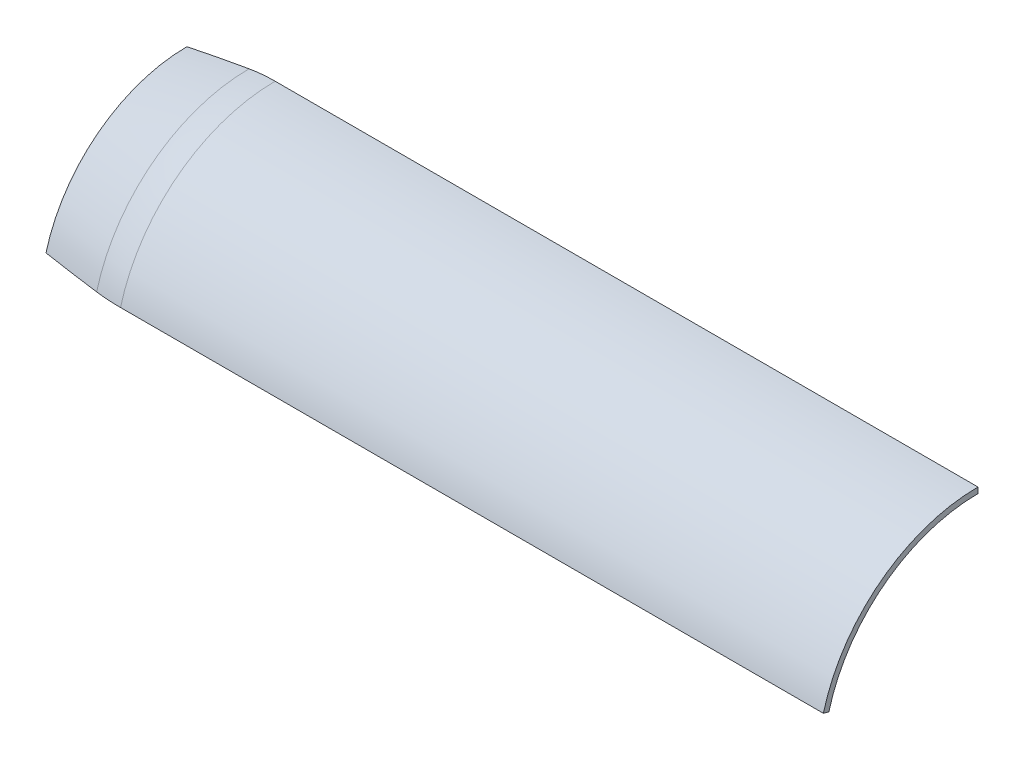
SolidWorks part; units mm, degrees
ref_plane "Front Plane" through (0, 0, 0) normal (0, 0, 1) x (1, 0, 0)
ref_plane "Top Plane" through (0, 0, 0) normal (0, 1, 0) x (1, 0, 0)
ref_plane "Right Plane" through (0, 0, 0) normal (1, 0, 0) x (0, 0, -1)
curve "Curve1"
  spline degree 3 poles (0, 0, 0) (-0.0123, 3.8916, 0) (-0.0274, 8.685, 0) (0.3616, 14.0857, 0) (0.5761, 16.0905, 0) (0.7825, 17.6048, 0) (0.9862, 18.8543, 0) (1.1887, 19.9315, 0) (1.3904, 20.8857, 0) (1.5917, 21.7465, 0) (1.7927, 22.5337, 0) (1.9935, 23.2611, 0) (2.1942, 23.9386, 0) (2.3947, 24.5739, 0) (2.5952, 25.1728, 0) (2.7956, 25.7401, 0) (2.9959, 26.2796, 0) (3.1962, 26.7943, 0) (3.3965, 27.2868, 0) (3.5967, 27.7594, 0) (3.7969, 28.2139, 0) (3.9971, 28.6519, 0) (4.1973, 29.0748, 0) (4.3974, 29.4838, 0) (4.5976, 29.8799, 0) (4.7977, 30.2641, 0) (4.9978, 30.6373, 0) (5.1979, 31.0001, 0) (5.398, 31.3533, 0) (5.5981, 31.6974, 0) (5.7982, 32.033, 0) (5.9983, 32.3606, 0) (6.1984, 32.6807, 0) (6.3985, 32.9935, 0) (6.5985, 33.2996, 0) (6.7986, 33.5993, 0) (6.9986, 33.8929, 0) (7.1987, 34.1806, 0) (7.3987, 34.4628, 0) (7.5988, 34.7397, 0) (7.7988, 35.0115, 0) (7.9989, 35.2785, 0) (8.1989, 35.5408, 0) (8.399, 35.7988, 0) (8.599, 36.0524, 0) (8.799, 36.3019, 0) (8.9991, 36.5476, 0) (9.1991, 36.7894, 0) (9.3991, 37.0275, 0) (9.5992, 37.2622, 0) (9.7992, 37.4934, 0) (9.9992, 37.7214, 0) (10.1992, 37.9461, 0) (10.3993, 38.1679, 0) (10.5993, 38.3866, 0) (10.7993, 38.6025, 0) (10.9993, 38.8156, 0) (11.1993, 39.026, 0) (11.3994, 39.2338, 0) (11.5994, 39.4391, 0) (11.7994, 39.6419, 0) (11.9994, 39.8422, 0) (12.1994, 40.0403, 0) (12.3995, 40.2361, 0) (12.5995, 40.4297, 0) (12.7995, 40.6212, 0) (12.9995, 40.8106, 0) (13.1995, 40.998, 0) (13.3995, 41.1834, 0) (13.5995, 41.3668, 0) (13.7995, 41.5484, 0) (13.9996, 41.7281, 0) (14.1996, 41.9061, 0) (14.3996, 42.0823, 0) (14.5996, 42.2568, 0) (14.7996, 42.4296, 0) (14.9996, 42.6008, 0) (15.1996, 42.7705, 0) (15.3996, 42.9385, 0) (15.5996, 43.1051, 0) (15.7996, 43.2701, 0) (15.9997, 43.4337, 0) (16.1997, 43.5959, 0) (16.3997, 43.7567, 0) (16.5997, 43.9161, 0) (16.7997, 44.0742, 0) (16.9997, 44.2309, 0) (17.1997, 44.3864, 0) (17.3997, 44.5406, 0) (17.5997, 44.6936, 0) (17.7997, 44.8453, 0) (17.9997, 44.9959, 0) (18.1997, 45.1453, 0) (18.3997, 45.2936, 0) (18.5997, 45.4407, 0) (18.7997, 45.5868, 0) (18.9997, 45.7317, 0) (19.1998, 45.8756, 0) (19.3998, 46.0185, 0) (19.5998, 46.1603, 0) (19.7998, 46.3011, 0) (19.9998, 46.4409, 0) (20.1998, 46.5797, 0) (20.3998, 46.7176, 0) (20.5998, 46.8546, 0) (20.7998, 46.9906, 0) (20.9998, 47.1257, 0) (21.1998, 47.2599, 0) (21.3998, 47.3932, 0) (21.5998, 47.5256, 0) (21.7998, 47.6572, 0) (21.9998, 47.788, 0) (22.1998, 47.9179, 0) (22.3998, 48.047, 0) (22.5998, 48.1753, 0) (22.7998, 48.3028, 0) (22.9998, 48.4295, 0) (23.1998, 48.5555, 0) (23.3998, 48.6807, 0) (23.5998, 48.8051, 0) (23.7998, 48.9288, 0) (23.9998, 49.0518, 0) (24.1998, 49.1741, 0) (24.3998, 49.2957, 0) (24.5998, 49.4165, 0) (24.7999, 49.5367, 0) (24.9999, 49.6562, 0) (25.1999, 49.7751, 0) (25.3999, 49.8933, 0) (25.5999, 50.0108, 0) (25.7999, 50.1277, 0) (25.9999, 50.2439, 0) (26.1999, 50.3596, 0) (26.3999, 50.4746, 0) (26.5999, 50.589, 0) (26.7999, 50.7028, 0) (26.9999, 50.8161, 0) (27.1999, 50.9287, 0) (27.3999, 51.0407, 0) (27.5999, 51.1522, 0) (27.7999, 51.2631, 0) (27.9999, 51.3735, 0) (28.1999, 51.4833, 0) (28.3999, 51.5926, 0) (28.5999, 51.7013, 0) (28.7999, 51.8095, 0) (28.9999, 51.9172, 0) (29.1999, 52.0243, 0) (29.3999, 52.131, 0) (29.5999, 52.2371, 0) (29.7999, 52.3428, 0) (29.9999, 52.4479, 0) (30.1999, 52.5526, 0) (30.3999, 52.6567, 0) (30.5999, 52.7604, 0) (30.7999, 52.8636, 0) (30.9999, 52.9664, 0) (31.1999, 53.0687, 0) (31.3999, 53.1705, 0) (31.5999, 53.2719, 0) (31.7999, 53.3728, 0) (31.9999, 53.4733, 0) (32.1999, 53.5733, 0) (32.3999, 53.6729, 0) (32.5999, 53.7721, 0) (32.7999, 53.8709, 0) (32.9999, 53.9692, 0) (33.1999, 54.0671, 0) (33.3999, 54.1646, 0) (33.5999, 54.2617, 0) (33.7999, 54.3584, 0) (33.9999, 54.4547, 0) (34.1999, 54.5506, 0) (34.3999, 54.6461, 0) (34.5999, 54.7412, 0) (34.7999, 54.836, 0) (34.9999, 54.9303, 0) (35.1999, 55.0243, 0) (35.3999, 55.1179, 0) (35.5999, 55.2111, 0) (35.7999, 55.304, 0) (35.9999, 55.3965, 0) (36.1999, 55.4887, 0) (36.3999, 55.5805, 0) (36.5999, 55.6719, 0) (36.7999, 55.763, 0) (36.9999, 55.8537, 0) (37.1999, 55.9441, 0) (37.3999, 56.0342, 0) (37.5999, 56.1239, 0) (37.7999, 56.2133, 0) (37.9999, 56.3024, 0) (38.1999, 56.3911, 0) (38.3999, 56.4795, 0) (38.5999, 56.5676, 0) (38.7999, 56.6554, 0) (38.9999, 56.7428, 0) (39.1999, 56.83, 0) (39.3999, 56.9168, 0) (39.5999, 57.0033, 0) (39.7999, 57.0896, 0) (39.9999, 57.1755, 0) (40.1999, 57.2611, 0) (40.3999, 57.3464, 0) (40.5999, 57.4314, 0) (40.7999, 57.5161, 0) (40.9999, 57.6006, 0) (41.1999, 57.6847, 0) (41.3999, 57.7686, 0) (41.6, 57.8522, 0) (41.8, 57.9355, 0) (42, 58.0185, 0) (42.2, 58.1012, 0) (42.4, 58.1837, 0) (42.6, 58.2659, 0) (42.8, 58.3479, 0) (43, 58.4295, 0) (43.2, 58.5109, 0) (43.4, 58.592, 0) (43.6, 58.6729, 0) (43.8, 58.7535, 0) (44, 58.8339, 0) (44.2, 58.914, 0) (44.4, 58.9938, 0) (44.6, 59.0734, 0) (44.8, 59.1528, 0) (45, 59.2319, 0) (45.2, 59.3107, 0) (45.4, 59.3893, 0) (45.6, 59.4677, 0) (45.8, 59.5458, 0) (46, 59.6237, 0) (46.2, 59.7014, 0) (46.4, 59.7788, 0) (46.6, 59.856, 0) (46.8, 59.9329, 0) (47, 60.0096, 0) (47.2, 60.0861, 0) (47.4, 60.1624, 0) (47.6, 60.2385, 0) (47.8, 60.3143, 0) (48, 60.3899, 0) (48.2, 60.4652, 0) (48.4, 60.5404, 0) (48.6, 60.6153, 0) (48.8, 60.6901, 0) (49, 60.7646, 0) (49.2, 60.8389, 0) (49.4, 60.913, 0) (49.6, 60.9869, 0) (49.8, 61.0605, 0) (50, 61.134, 0) (50.2, 61.2072, 0) (50.4, 61.2803, 0) (50.6, 61.3531, 0) (50.8, 61.4258, 0) (51, 61.4982, 0) (51.2, 61.5705, 0) (51.4, 61.6426, 0) (51.6, 61.7144, 0) (51.8, 61.7861, 0) (52, 61.8575, 0) (52.2, 61.9288, 0) (52.4, 61.9999, 0) (52.6, 62.0708, 0) (52.8, 62.1415, 0) (53, 62.212, 0) (53.2, 62.2824, 0) (53.4, 62.3525, 0) (53.6, 62.4225, 0) (53.8, 62.4923, 0) (54, 62.5619, 0) (54.2, 62.6313, 0) (54.4, 62.7006, 0) (54.6, 62.7696, 0) (54.8, 62.8385, 0) (55, 62.9072, 0) (55.2, 62.9758, 0) (55.4, 63.0441, 0) (55.6, 63.1123, 0) (55.8, 63.1803, 0) (56, 63.2482, 0) (56.2, 63.3159, 0) (56.4, 63.3834, 0) (56.6, 63.4507, 0) (56.8, 63.5179, 0) (57, 63.5849, 0) (57.2, 63.6518, 0) (57.4, 63.7185, 0) (57.6, 63.785, 0) (57.8, 63.8513, 0) (58, 63.9175, 0) (58.2, 63.9836, 0) (58.4, 64.0495, 0) (58.6, 64.1152, 0) (58.8, 64.1808, 0) (59, 64.2462, 0) (59.2, 64.3114, 0) (59.4, 64.3765, 0) (59.6, 64.4415, 0) (59.8, 64.5063, 0) (60, 64.5709, 0) (60.2, 64.6354, 0) (60.4, 64.6998, 0) (60.6, 64.764, 0) (60.8, 64.828, 0) (61, 64.8919, 0) (61.2, 64.9557, 0) (61.4, 65.0193, 0) (61.6, 65.0827, 0) (61.8, 65.1461, 0) (62, 65.2092, 0) (62.2, 65.2723, 0) (62.4, 65.3352, 0) (62.6, 65.3979, 0) (62.8, 65.4605, 0) (63, 65.523, 0) (63.2, 65.5853, 0) (63.4, 65.6475, 0) (63.6, 65.7096, 0) (63.8, 65.7715, 0) (64, 65.8333, 0) (64.2, 65.895, 0) (64.4, 65.9565, 0) (64.6, 66.0179, 0) (64.8, 66.0791, 0) (65, 66.1402, 0) (65.2, 66.2012, 0) (65.4, 66.2621, 0) (65.6, 66.3228, 0) (65.8, 66.3834, 0) (66, 66.4439, 0) (66.2, 66.5042, 0) (66.4, 66.5644, 0) (66.6, 66.6245, 0) (66.8, 66.6845, 0) (67, 66.7443, 0) (67.2, 66.804, 0) (67.4, 66.8636, 0) (67.6, 66.923, 0) (67.8, 66.9824, 0) (68, 67.0416, 0) (68.2, 67.1007, 0) (68.4, 67.1597, 0) (68.6, 67.2185, 0) (68.8, 67.2772, 0) (69, 67.3359, 0) (69.2, 67.3943, 0) (69.4, 67.4527, 0) (69.6, 67.511, 0) (69.8, 67.5691, 0) (70, 67.6271, 0) (70.2, 67.6851, 0) (70.4, 67.7428, 0) (70.6, 67.8005, 0) (70.8, 67.8581, 0) (71, 67.9155, 0) (71.2, 67.9729, 0) (71.4, 68.0301, 0) (71.6, 68.0872, 0) (71.8, 68.1442, 0) (72, 68.2011, 0) (72.2, 68.2579, 0) (72.4, 68.3145, 0) (72.6, 68.3711, 0) (72.8, 68.4276, 0) (73, 68.4839, 0) (73.2, 68.5401, 0) (73.4, 68.5963, 0) (73.6, 68.6523, 0) (73.8, 68.7082, 0) (74, 68.764, 0) (74.2, 68.8197, 0) (74.4, 68.8753, 0) (74.6, 68.9308, 0) (74.8, 68.9862, 0) (75, 69.0415, 0) (75.2, 69.0966, 0) (75.4, 69.1517, 0) (75.6, 69.2067, 0) (75.8, 69.2616, 0) (76, 69.3164, 0) (76.2, 69.371, 0) (76.4, 69.4256, 0) (76.6, 69.4801, 0) (76.8, 69.5344, 0) (77, 69.5887, 0) (77.2, 69.6429, 0) (77.4, 69.697, 0) (77.6, 69.751, 0) (77.8, 69.8048, 0) (78, 69.8586, 0) (78.2, 69.9123, 0) (78.4, 69.9659, 0) (78.6, 70.0194, 0) (78.8, 70.0728, 0) (79, 70.1261, 0) (79.2, 70.1793, 0) (79.4, 70.2324, 0) (79.6, 70.2855, 0) (79.8, 70.3384, 0) (80, 70.3912, 0) (80.2, 70.444, 0) (80.4, 70.4966, 0) (80.6, 70.5492, 0) (80.8, 70.6017, 0) (81, 70.6541, 0) (81.2, 70.7064, 0) (81.4, 70.7586, 0) (81.6, 70.8107, 0) (81.8, 70.8627, 0) (82, 70.9146, 0) (82.2, 70.9665, 0) (82.4, 71.0182, 0) (82.6, 71.0699, 0) (82.8, 71.1215, 0) (83, 71.173, 0) (83.2, 71.2244, 0) (83.4, 71.2757, 0) (83.6, 71.3269, 0) (83.8, 71.3781, 0) (84, 71.4291, 0) (84.2, 71.4801, 0) (84.4, 71.531, 0) (84.6, 71.5818, 0) (84.8, 71.6325, 0) (85, 71.6832, 0) (85.2, 71.7337, 0) (85.4, 71.7842, 0) (85.6, 71.8346, 0) (85.8, 71.8849, 0) (86, 71.9351, 0) (86.2, 71.9853, 0) (86.4, 72.0354, 0) (86.6, 72.0853, 0) (86.8, 72.1352, 0) (87, 72.1851, 0) (87.2, 72.2348, 0) (87.4, 72.2845, 0) (87.6, 72.3341, 0) (87.8, 72.3836, 0) (88, 72.433, 0) (88.2, 72.4823, 0) (88.4, 72.5316, 0) (88.6, 72.5808, 0) (88.8, 72.6299, 0) (89, 72.6789, 0) (89.2, 72.7279, 0) (89.4, 72.7768, 0) (89.6, 72.8256, 0) (89.8, 72.8743, 0) (90, 72.923, 0) (90.2, 72.9716, 0) (90.4, 73.0201, 0) (90.6, 73.0685, 0) (90.8, 73.1168, 0) (91, 73.1651, 0) (91.2, 73.2133, 0) (91.4, 73.2614, 0) (91.6, 73.3095, 0) (91.8, 73.3575, 0) (92, 73.4054, 0) (92.2, 73.4532, 0) (92.4, 73.501, 0) (92.6, 73.5487, 0) (92.8, 73.5963, 0) (93, 73.6439, 0) (93.2, 73.6913, 0) (93.4, 73.7387, 0) (93.6, 73.7861, 0) (93.8, 73.8333, 0) (94, 73.8805, 0) (94.2, 73.9276, 0) (94.4, 73.9747, 0) (94.6, 74.0217, 0) (94.8, 74.0686, 0) (95, 74.1154, 0) (95.2, 74.1622, 0) (95.4, 74.2089, 0) (95.6, 74.2556, 0) (95.8, 74.3021, 0) (96, 74.3486, 0) (96.2, 74.3951, 0) (96.4, 74.4414, 0) (96.6, 74.4877, 0) (96.8, 74.534, 0) (97, 74.5801, 0) (97.2, 74.6262, 0) (97.4, 74.6723, 0) (97.6, 74.7182, 0) (97.8, 74.7641, 0) (98, 74.81, 0) (98.2, 74.8557, 0) (98.4, 74.9014, 0) (98.6, 74.9471, 0) (98.8, 74.9926, 0) (99, 75.0382, 0) (99.2, 75.0836, 0) (99.4, 75.129, 0) (99.6, 75.1743, 0) (99.8, 75.2196, 0) (100, 75.2647, 0) (100.2, 75.3099, 0) (100.4, 75.3549, 0) (100.6, 75.3999, 0) (100.8, 75.4449, 0) (101, 75.4898, 0) (101.2, 75.5346, 0) (101.4, 75.5793, 0) (101.6, 75.624, 0) (101.8, 75.6686, 0) (102, 75.7132, 0) (102.2, 75.7577, 0) (102.4, 75.8022, 0) (102.6, 75.8465, 0) (102.8, 75.8909, 0) (103, 75.9351, 0) (103.2, 75.9793, 0) (103.4, 76.0235, 0) (103.6, 76.0676, 0) (103.8, 76.1116, 0) (104, 76.1556, 0) (104.2, 76.1995, 0) (104.4, 76.2433, 0) (104.6, 76.2871, 0) (104.8, 76.3308, 0) (105, 76.3745, 0) (105.2, 76.4181, 0) (105.4, 76.4617, 0) (105.6, 76.5052, 0) (105.8, 76.5486, 0) (106, 76.592, 0) (106.2, 76.6353, 0) (106.4, 76.6786, 0) (106.6, 76.7218, 0) (106.8, 76.7649, 0) (107, 76.808, 0) (107.2, 76.8511, 0) (107.4, 76.8941, 0) (107.6, 76.937, 0) (107.8, 76.9799, 0) (108, 77.0227, 0) (108.2, 77.0655, 0) (108.4, 77.1082, 0) (108.6, 77.1508, 0) (108.8, 77.1934, 0) (109, 77.236, 0) (109.2, 77.2784, 0) (109.4, 77.3209, 0) (109.6, 77.3633, 0) (109.8, 77.4056, 0) (110, 77.4479, 0) (110.2, 77.4901, 0) (110.4, 77.5322, 0) (110.6, 77.5743, 0) (110.8, 77.6164, 0) (111, 77.6584, 0) (111.2, 77.7004, 0) (111.4, 77.7423, 0) (111.6, 77.7841, 0) (111.8, 77.8259, 0) (112, 77.8676, 0) (112.2, 77.9093, 0) (112.4, 77.951, 0) (112.6, 77.9925, 0) (112.8, 78.0341, 0) (113, 78.0756, 0) (113.2, 78.117, 0) (113.4, 78.1584, 0) (113.6, 78.1997, 0) (113.8, 78.241, 0) (114, 78.2822, 0) (114.2, 78.3234, 0) (114.4, 78.3645, 0) (114.6, 78.4056, 0) (114.8, 78.4466, 0) (115, 78.4876, 0) (115.2, 78.5285, 0) (115.4, 78.5694, 0) (115.6, 78.6102, 0) (115.8, 78.651, 0) (116, 78.6917, 0) (116.2, 78.7324, 0) (116.4, 78.773, 0) (116.6, 78.8136, 0) (116.8, 78.8541, 0) (117, 78.8946, 0) (117.2, 78.935, 0) (117.4, 78.9754, 0) (117.6, 79.0158, 0) (117.8, 79.0561, 0) (118, 79.0963, 0) (118.2, 79.1365, 0) (118.4, 79.1766, 0) (118.6, 79.2167, 0) (118.8, 79.2568, 0) (119, 79.2968, 0) (119.2, 79.3368, 0) (119.4, 79.3767, 0) (119.6, 79.4165, 0) (119.8, 79.4564, 0) (120, 79.4961, 0) (120.2, 79.5358, 0) (120.4, 79.5755, 0) (120.6, 79.6152, 0) (120.8, 79.6547, 0) (121, 79.6943, 0) (121.2, 79.7338, 0) (121.4, 79.7732, 0) (121.6, 79.8126, 0) (121.8, 79.852, 0) (122, 79.8913, 0) (122.2, 79.9306, 0) (122.4, 79.9698, 0) (122.6, 80.009, 0) (122.8, 80.0481, 0) (123, 80.0872, 0) (123.2, 80.1262, 0) (123.4, 80.1652, 0) (123.6, 80.2042, 0) (123.8, 80.2431, 0) (124, 80.282, 0) (124.2, 80.3208, 0) (124.4, 80.3596, 0) (124.6, 80.3983, 0) (124.8, 80.437, 0) (125, 80.4757, 0) (125.2, 80.5143, 0) (125.4, 80.5528, 0) (125.6, 80.5914, 0) (125.8, 80.6298, 0) (126, 80.6683, 0) (126.2, 80.7067, 0) (126.4, 80.745, 0) (126.6, 80.7833, 0) (126.8, 80.8216, 0) (127, 80.8598, 0) (127.2, 80.898, 0) (127.4, 80.9361, 0) (127.6, 80.9742, 0) (127.8, 81.0123, 0) (128, 81.0503, 0) (128.2, 81.0883, 0) (128.4, 81.1262, 0) (128.6, 81.1641, 0) (128.8, 81.2019, 0) (129, 81.2397, 0) (129.2, 81.2775, 0) (129.4, 81.3152, 0) (129.6, 81.3529, 0) (129.8, 81.3906, 0) (130, 81.4282, 0) (130.2, 81.4657, 0) (130.4, 81.5032, 0) (130.6, 81.5407, 0) (130.8, 81.5782, 0) (131, 81.6156, 0) (131.2, 81.6529, 0) (131.4, 81.6902, 0) (131.6, 81.7275, 0) (131.8, 81.7648, 0) (132, 81.802, 0) (132.2, 81.8391, 0) (132.4, 81.8763, 0) (132.6, 81.9133, 0) (132.8, 81.9504, 0) (133, 81.9874, 0) (133.2, 82.0244, 0) (133.4, 82.0613, 0) (133.6, 82.0982, 0) (133.8, 82.135, 0) (134, 82.1718, 0) (134.2, 82.2086, 0) (134.4, 82.2454, 0) (134.6, 82.282, 0) (134.8, 82.3187, 0) (135, 82.3553, 0) (135.2, 82.3919, 0) (135.4, 82.4285, 0) (135.6, 82.465, 0) (135.8, 82.5014, 0) (136, 82.5379, 0) (136.2, 82.5743, 0) (136.4, 82.6106, 0) (136.6, 82.6469, 0) (136.8, 82.6832, 0) (137, 82.7195, 0) (137.2, 82.7557, 0) (137.4, 82.7919, 0) (137.6, 82.828, 0) (137.8, 82.8641, 0) (138, 82.9001, 0) (138.2, 82.9362, 0) (138.4, 82.9722, 0) (138.6, 83.0081, 0) (138.8, 83.044, 0) (139, 83.0799, 0) (139.2, 83.1158, 0) (139.4, 83.1516, 0) (139.6, 83.1873, 0) (139.8, 83.2231, 0) (140, 83.2588, 0) (140.2, 83.2944, 0) (140.4, 83.3301, 0) (140.6, 83.3657, 0) (140.8, 83.4012, 0) (141, 83.4367, 0) (141.2, 83.4722, 0) (141.4, 83.5077, 0) (141.6, 83.5431, 0) (141.8, 83.5785, 0) (142, 83.6138, 0) (142.2, 83.6491, 0) (142.4, 83.6844, 0) (142.6, 83.7197, 0) (142.8, 83.7549, 0) (143, 83.79, 0) (143.2, 83.8252, 0) (143.4, 83.8603, 0) (143.6, 83.8954, 0) (143.8, 83.9304, 0) (144, 83.9654, 0) (144.2, 84.0004, 0) (144.4, 84.0353, 0) (144.6, 84.0702, 0) (144.8, 84.1051, 0) (145, 84.1399, 0) (145.2, 84.1747, 0) (145.4, 84.2095, 0) (145.6, 84.2442, 0) (145.8, 84.2789, 0) (146, 84.3136, 0) (146.2, 84.3482, 0) (146.4, 84.3828, 0) (146.6, 84.4174, 0) (146.8, 84.4519, 0) (147, 84.4864, 0) (147.2, 84.5209, 0) (147.4, 84.5553, 0) (147.6, 84.5897, 0) (147.8, 84.6241, 0) (148, 84.6584, 0) (148.2, 84.6927, 0) (148.4, 84.727, 0) (148.6, 84.7612, 0) (148.8, 84.7954, 0) (149, 84.8296, 0) (149.2, 84.8638, 0) (149.4, 84.8979, 0) (149.6, 84.9319, 0) (149.8, 84.966, 0) (149.9333, 84.9887, 0) (150, 85, 0) knots 0 0 0 0 0.061462 0.075706 0.085548 0.093322 0.099856 0.105554 0.110643 0.115268 0.119525 0.123482 0.127192 0.130691 0.13401 0.137173 0.140199 0.143104 0.145901 0.148602 0.151215 0.15375 0.156213 0.158609 0.160946 0.163227 0.165456 0.167638 0.169775 0.171871 0.173928 0.17595 0.177937 0.179893 0.181819 0.183716 0.185587 0.187433 0.189255 0.191054 0.192831 0.194589 0.196326 0.198045 0.199747 0.201431 0.2031 0.204753 0.206391 0.208015 0.209626 0.211223 0.212808 0.214381 0.215942 0.217493 0.219032 0.220561 0.22208 0.22359 0.225091 0.226582 0.228065 0.229539 0.231006 0.232464 0.233915 0.235359 0.236795 0.238225 0.239648 0.241065 0.242475 0.243879 0.245277 0.24667 0.248057 0.249438 0.250814 0.252185 0.253551 0.254913 0.256269 0.257621 0.258968 0.260311 0.26165 0.262984 0.264315 0.265641 0.266964 0.268282 0.269598 0.270909 0.272217 0.273522 0.274823 0.276121 0.277416 0.278707 0.279996 0.281281 0.282564 0.283843 0.28512 0.286394 0.287666 0.288935 0.290201 0.291465 0.292726 0.293985 0.295241 0.296495 0.297747 0.298996 0.300243 0.301489 0.302732 0.303972 0.305211 0.306448 0.307683 0.308916 0.310147 0.311376 0.312604 0.313829 0.315053 0.316275 0.317495 0.318714 0.319931 0.321147 0.32236 0.323573 0.324783 0.325993 0.3272 0.328406 0.329611 0.330815 0.332017 0.333217 0.334416 0.335614 0.336811 0.338006 0.3392 0.340393 0.341584 0.342775 0.343964 0.345152 0.346339 0.347524 0.348709 0.349892 0.351074 0.352256 0.353436 0.354615 0.355793 0.35697 0.358146 0.359321 0.360495 0.361668 0.36284 0.364011 0.365182 0.366351 0.36752 0.368687 0.369854 0.37102 0.372185 0.373349 0.374512 0.375674 0.376836 0.377997 0.379157 0.380316 0.381475 0.382632 0.383789 0.384946 0.386101 0.387256 0.38841 0.389563 0.390716 0.391868 0.393019 0.39417 0.39532 0.396469 0.397618 0.398766 0.399913 0.40106 0.402206 0.403351 0.404496 0.40564 0.406784 0.407927 0.409069 0.410211 0.411353 0.412493 0.413633 0.414773 0.415912 0.417051 0.418189 0.419326 0.420463 0.4216 0.422736 0.423871 0.425006 0.426141 0.427275 0.428408 0.429541 0.430674 0.431806 0.432937 0.434068 0.435199 0.436329 0.437459 0.438588 0.439717 0.440846 0.441974 0.443101 0.444229 0.445355 0.446482 0.447608 0.448733 0.449858 0.450983 0.452107 0.453231 0.454355 0.455478 0.456601 0.457723 0.458845 0.459967 0.461088 0.462209 0.46333 0.46445 0.46557 0.46669 0.467809 0.468928 0.470046 0.471164 0.472282 0.4734 0.474517 0.475634 0.47675 0.477866 0.478982 0.480098 0.481213 0.482328 0.483443 0.484557 0.485671 0.486785 0.487898 0.489011 0.490124 0.491237 0.492349 0.493461 0.494573 0.495684 0.496796 0.497906 0.499017 0.500127 0.501237 0.502347 0.503457 0.504566 0.505675 0.506784 0.507892 0.509001 0.510109 0.511216 0.512324 0.513431 0.514538 0.515645 0.516752 0.517858 0.518964 0.52007 0.521175 0.522281 0.523386 0.524491 0.525595 0.5267 0.527804 0.528908 0.530012 0.531116 0.532219 0.533322 0.534425 0.535528 0.53663 0.537733 0.538835 0.539937 0.541038 0.54214 0.543241 0.544342 0.545443 0.546544 0.547644 0.548745 0.549845 0.550945 0.552044 0.553144 0.554243 0.555342 0.556441 0.55754 0.558639 0.559737 0.560836 0.561934 0.563032 0.564129 0.565227 0.566324 0.567421 0.568518 0.569615 0.570712 0.571809 0.572905 0.574001 0.575097 0.576193 0.577289 0.578384 0.57948 0.580575 0.58167 0.582765 0.58386 0.584954 0.586049 0.587143 0.588237 0.589331 0.590425 0.591519 0.592612 0.593706 0.594799 0.595892 0.596985 0.598078 0.59917 0.600263 0.601355 0.602448 0.60354 0.604632 0.605724 0.606815 0.607907 0.608998 0.61009 0.611181 0.612272 0.613363 0.614453 0.615544 0.616635 0.617725 0.618815 0.619905 0.620995 0.622085 0.623175 0.624265 0.625354 0.626443 0.627533 0.628622 0.629711 0.6308 0.631888 0.632977 0.634066 0.635154 0.636242 0.637331 0.638419 0.639507 0.640594 0.641682 0.64277 0.643857 0.644945 0.646032 0.647119 0.648206 0.649293 0.65038 0.651467 0.652553 0.65364 0.654726 0.655813 0.656899 0.657985 0.659071 0.660157 0.661243 0.662328 0.663414 0.664499 0.665585 0.66667 0.667755 0.66884 0.669925 0.67101 0.672095 0.67318 0.674264 0.675349 0.676433 0.677518 0.678602 0.679686 0.68077 0.681854 0.682938 0.684022 0.685105 0.686189 0.687272 0.688356 0.689439 0.690522 0.691605 0.692688 0.693771 0.694854 0.695937 0.69702 0.698102 0.699185 0.700267 0.70135 0.702432 0.703514 0.704596 0.705678 0.70676 0.707842 0.708924 0.710006 0.711087 0.712169 0.71325 0.714332 0.715413 0.716494 0.717575 0.718656 0.719737 0.720818 0.721899 0.72298 0.724061 0.725141 0.726222 0.727302 0.728382 0.729463 0.730543 0.731623 0.732703 0.733783 0.734863 0.735943 0.737023 0.738103 0.739182 0.740262 0.741341 0.742421 0.7435 0.744579 0.745659 0.746738 0.747817 0.748896 0.749975 0.751054 0.752133 0.753211 0.75429 0.755369 0.756447 0.757526 0.758604 0.759682 0.760761 0.761839 0.762917 0.763995 0.765073 0.766151 0.767229 0.768307 0.769385 0.770462 0.77154 0.772618 0.773695 0.774773 0.77585 0.776927 0.778005 0.779082 0.780159 0.781236 0.782313 0.78339 0.784467 0.785544 0.786621 0.787698 0.788774 0.789851 0.790928 0.792004 0.793081 0.794157 0.795233 0.79631 0.797386 0.798462 0.799538 0.800614 0.80169 0.802766 0.803842 0.804918 0.805994 0.80707 0.808145 0.809221 0.810296 0.811372 0.812447 0.813523 0.814598 0.815674 0.816749 0.817824 0.818899 0.819974 0.821049 0.822124 0.823199 0.824274 0.825349 0.826424 0.827499 0.828573 0.829648 0.830723 0.831797 0.832872 0.833946 0.835021 0.836095 0.837169 0.838244 0.839318 0.840392 0.841466 0.84254 0.843614 0.844688 0.845762 0.846836 0.84791 0.848984 0.850058 0.851131 0.852205 0.853279 0.854352 0.855426 0.856499 0.857573 0.858646 0.859719 0.860793 0.861866 0.862939 0.864012 0.865085 0.866159 0.867232 0.868305 0.869378 0.87045 0.871523 0.872596 0.873669 0.874742 0.875814 0.876887 0.87796 0.879032 0.880105 0.881177 0.88225 0.883322 0.884395 0.885467 0.886539 0.887611 0.888684 0.889756 0.890828 0.8919 0.892972 0.894044 0.895116 0.896188 0.89726 0.898332 0.899404 0.900475 0.901547 0.902619 0.90369 0.904762 0.905834 0.906905 0.907977 0.909048 0.91012 0.911191 0.912262 0.913334 0.914405 0.915476 0.916548 0.917619 0.91869 0.919761 0.920832 0.921903 0.922974 0.924045 0.925116 0.926187 0.927258 0.928329 0.929399 0.93047 0.931541 0.932612 0.933682 0.934753 0.935823 0.936894 0.937965 0.939035 0.940105 0.941176 0.942246 0.943317 0.944387 0.945457 0.946527 0.947598 0.948668 0.949738 0.950808 0.951878 0.952948 0.954018 0.955088 0.956158 0.957228 0.958298 0.959368 0.960438 0.961508 0.962577 0.963647 0.964717 0.965786 0.966856 0.967926 0.968995 0.970065 0.971134 0.972204 0.973273 0.974343 0.975412 0.976481 0.977551 0.97862 0.979689 0.980759 0.981828 0.982897 0.983966 0.985035 0.986104 0.987173 0.988242 0.989311 0.99038 0.991449 0.992518 0.993587 0.994656 0.995725 0.996794 0.997863 0.998931 1 1 1 1
sketch "Sketch1" plane through (0, 0, 0) normal (0, 0, 1) x (1, 0, 0)
  line L0 (0, 0) -> (3, 0)
  line L1 (3, 0.0095) -> (3, 0)
  line L3 (150, 85) -> (530, 85)
  line L4 (150, 81.9569) -> (530, 81.9569)
  line L5 (530, 81.9569) -> (530, 85)
  line L6 (0, 0) -> (686.3935, 0) construction
  spline S0 degree 3 poles (-4988.3045, -127.8298) (181.331, -218.097) (-7.7458, -98.4721) (0.3616, 14.0857) (0.5761, 16.0905) (0.7825, 17.6048) (0.9862, 18.8543) (1.1887, 19.9315) (1.3904, 20.8857) (1.5917, 21.7465) (1.7927, 22.5337) (1.9935, 23.2611) (2.2538, 24.14) (2.5806, 25.1462) (2.9836, 26.2595) (3.3859, 27.2713) (3.7877, 28.2016) (4.1891, 29.0648) (4.5903, 29.8717) (5.0533, 30.7478) (5.5832, 31.6835) (6.1854, 32.6697) (6.7872, 33.5906) (7.4515, 34.5461) (8.1828, 35.531) (8.9851, 36.54) (9.8503, 37.5625) (10.7826, 38.5957) (11.785, 39.6369) (12.851, 40.6804) (13.984, 41.7246) (15.1862, 42.7682) (16.388, 43.7553) (17.6544, 44.7435) (18.9876, 45.7315) (20.3892, 46.7179) (21.7905, 47.6579) (23.2571, 48.5984) (24.7904, 49.5382) (26.3916, 50.4762) (28.0583, 51.4122) (29.7917, 52.3451) (31.5927, 53.2742) (33.4594, 54.1996) (35.3929, 55.1207) (37.4597, 56.0672) (39.5933, 57.0066) (41.8602, 57.9666) (44.1937, 58.9175) (46.6606, 59.8853) (49.2604, 60.8677) (51.994, 61.8617) (54.861, 62.8656) (57.7946, 63.8556) (60.8615, 64.8536) (64.0615, 65.8584) (67.4615, 66.8882) (70.9951, 67.9202) (74.6621, 68.9539) (78.4621, 69.9886) (82.4622, 71.0404) (86.6623, 72.1071) (91.0624, 73.1864) (95.6625, 74.2764) (100.4626, 75.3753) (105.4628, 76.4816) (110.6629, 77.5938) (116.063, 78.7107) (121.6632, 79.8312) (127.5299, 80.9671) (133.6633, 82.1162) (140.0634, 83.2764) (145.1985, 84.1774) (148.3332, 84.7158) (149.3333, 84.8865) (149.6, 84.9319) (210.4736, 95.2955) (272.2046, 100.2158) (-505.3505, 5038.0754) knots -1.697374 -1.697374 -1.697374 -1.697374 0.061462 0.075706 0.085548 0.093322 0.099856 0.105554 0.110643 0.115268 0.119525 0.123482 0.127192 0.13401 0.140199 0.145901 0.151215 0.156213 0.160946 0.165456 0.171871 0.177937 0.183716 0.189255 0.196326 0.2031 0.209626 0.217493 0.225091 0.232464 0.241065 0.249438 0.257621 0.265641 0.274823 0.283843 0.292726 0.301489 0.311376 0.321147 0.330815 0.341584 0.352256 0.36284 0.374512 0.386101 0.398766 0.411353 0.425006 0.438588 0.453231 0.468928 0.484557 0.501237 0.517858 0.535528 0.554243 0.574001 0.593706 0.614453 0.636242 0.659071 0.682938 0.707842 0.733783 0.760761 0.788774 0.817824 0.84791 0.879032 0.912262 0.946527 0.981828 0.994656 0.996794 0.997863 0.998931 1.972677 1.972677 1.972677 1.972677 only from (0, 0) to (150, 85) construction
  spline S1 degree 3 poles (0, 0) (-0.0123, 3.8916) (-0.0274, 8.685) (0.3616, 14.0857) (0.5761, 16.0905) (0.7825, 17.6048) (0.9862, 18.8543) (1.1887, 19.9315) (1.3904, 20.8857) (1.5917, 21.7465) (1.7927, 22.5337) (1.9935, 23.2611) (2.2538, 24.14) (2.5806, 25.1462) (2.9836, 26.2595) (3.3859, 27.2713) (3.7877, 28.2016) (4.1891, 29.0648) (4.5903, 29.8717) (5.0533, 30.7478) (5.5832, 31.6835) (6.1854, 32.6697) (6.7872, 33.5906) (7.4515, 34.5461) (8.1828, 35.531) (8.9851, 36.54) (9.8503, 37.5625) (10.7826, 38.5957) (11.785, 39.6369) (12.851, 40.6804) (13.984, 41.7246) (15.1862, 42.7682) (16.388, 43.7553) (17.6544, 44.7435) (18.9876, 45.7315) (20.3892, 46.7179) (21.7905, 47.6579) (23.2571, 48.5984) (24.7904, 49.5382) (26.3916, 50.4762) (28.0583, 51.4122) (29.7917, 52.3451) (31.5927, 53.2742) (33.4594, 54.1996) (35.3929, 55.1207) (37.4597, 56.0672) (39.5933, 57.0066) (41.8602, 57.9666) (44.1937, 58.9175) (46.6606, 59.8853) (49.2604, 60.8677) (51.994, 61.8617) (54.861, 62.8656) (57.7946, 63.8556) (60.8615, 64.8536) (64.0615, 65.8584) (67.4615, 66.8882) (70.9951, 67.9202) (74.6621, 68.9539) (78.4621, 69.9886) (82.4622, 71.0404) (86.6623, 72.1071) (91.0624, 73.1864) (95.6625, 74.2764) (100.4626, 75.3753) (105.4628, 76.4816) (110.6629, 77.5938) (116.063, 78.7107) (121.6632, 79.8312) (127.5299, 80.9671) (133.6633, 82.1162) (140.0634, 83.2764) (145.1985, 84.1774) (148.3332, 84.7158) (149.4, 84.8979) (149.7333, 84.9547) (149.9333, 84.9887) (150, 85) knots 0 0 0 0 0.061462 0.075706 0.085548 0.093322 0.099856 0.105554 0.110643 0.115268 0.119525 0.123482 0.127192 0.13401 0.140199 0.145901 0.151215 0.156213 0.160946 0.165456 0.171871 0.177937 0.183716 0.189255 0.196326 0.2031 0.209626 0.217493 0.225091 0.232464 0.241065 0.249438 0.257621 0.265641 0.274823 0.283843 0.292726 0.301489 0.311376 0.321147 0.330815 0.341584 0.352256 0.36284 0.374512 0.386101 0.398766 0.411353 0.425006 0.438588 0.453231 0.468928 0.484557 0.501237 0.517858 0.535528 0.554243 0.574001 0.593706 0.614453 0.636242 0.659071 0.682938 0.707842 0.733783 0.760761 0.788774 0.817824 0.84791 0.879032 0.912262 0.946527 0.981828 0.994656 0.996794 0.998931 1 1 1 1
  spline S2 degree 1 poles (3, 0.0095) (150.5029, 82.0425) knots 0 0 1 1 construction
  spline S3 degree 3 poles (3, 0.0095) (2.9938, 1.972) (2.982, 5.9191) (3.1454, 11.707) (3.6738, 17.3485) (4.827, 22.758) (6.7674, 27.8489) (10.4623, 34.1061) (16.9323, 40.8089) (26.3776, 47.2586) (36.673, 52.5723) (47.4414, 57.081) (62.1775, 62.3104) (81.0422, 67.7575) (104.0182, 73.2189) (126.9821, 77.894) (142.3896, 80.66) (150.1676, 81.9854) (150.3773, 82.0211) (150.5029, 82.0425) knots 0 0 0 0 0.03125 0.0625 0.09375 0.125 0.15625 0.1875 0.25 0.3125 0.375 0.4375 0.5 0.625 0.75 0.875 0.996634 0.99798 1 1 1 1 only from (3, 0.0095) to (150, 81.9569)
  dimension "D2" = 380
  dimension "D1" = 3
revolve "Revolve1" add sketch "Sketch1" angle 75 about L6
fillet "Fillet1" radius 80 1 edges at (150, 65.0207, 49.8922)
fillet "Fillet2" radius 80 1 edges at (150, 67.435, 51.7447)
sketch "Sketch3" plane through (0, 0, 0) normal (0, 1, 0) x (1, 0, 0)
  line L1 (-110, -104.4531) -> (110, -104.4531)
  line L2 (-110, -104.4531) -> (-110, 104.4531)
  line L3 (-110, 104.4531) -> (110, 104.4531)
  line L4 (110, -104.4531) -> (110, 104.4531)
  line L5 (-110, -104.4531) -> (110, 104.4531) construction
  line L6 (-110, 104.4531) -> (110, -104.4531) construction
  point P0 (0, 0)
  dimension "D1" = 110
extrude "Cut-Extrude3" cut sketch "Sketch3" along normal blind 159
